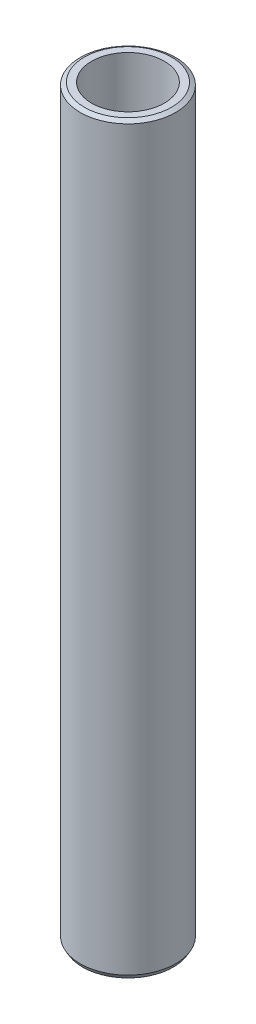
SolidWorks part; units mm, degrees
ref_plane "Front Plane" through (0, 0, 0) normal (0, 0, 1) x (1, 0, 0)
ref_plane "Top Plane" through (0, 0, 0) normal (0, 1, 0) x (1, 0, 0)
ref_plane "Right Plane" through (0, 0, 0) normal (1, 0, 0) x (0, 0, -1)
sketch "Sketch1" plane through (0, 0, 0) normal (0, 1, 0) x (1, 0, 0)
  circle A0 centre (0, 0) radius 30
  dimension "SHAFT_OD" = 60
extrude "Boss-Extrude1" add sketch "Sketch1" along normal blind 467.6416
sketch "Sketch2" plane through (0, 0, 0) normal (0, 1, 0) x (1, 0, 0)
  circle A0 centre (0, 0) radius 22.8713
  dimension "BORE_D" = 45.7427
extrude "Cut-Extrude1" cut sketch "Sketch2" along normal through all
chamfer "Chamfer1" distance 1.5128 angle 60 2 edges at (0, 467.6416, 30) (0, 0, 30) first distance on face at (0, 467.6416, 30) first distance on face at (0, 0, 22.8713)
